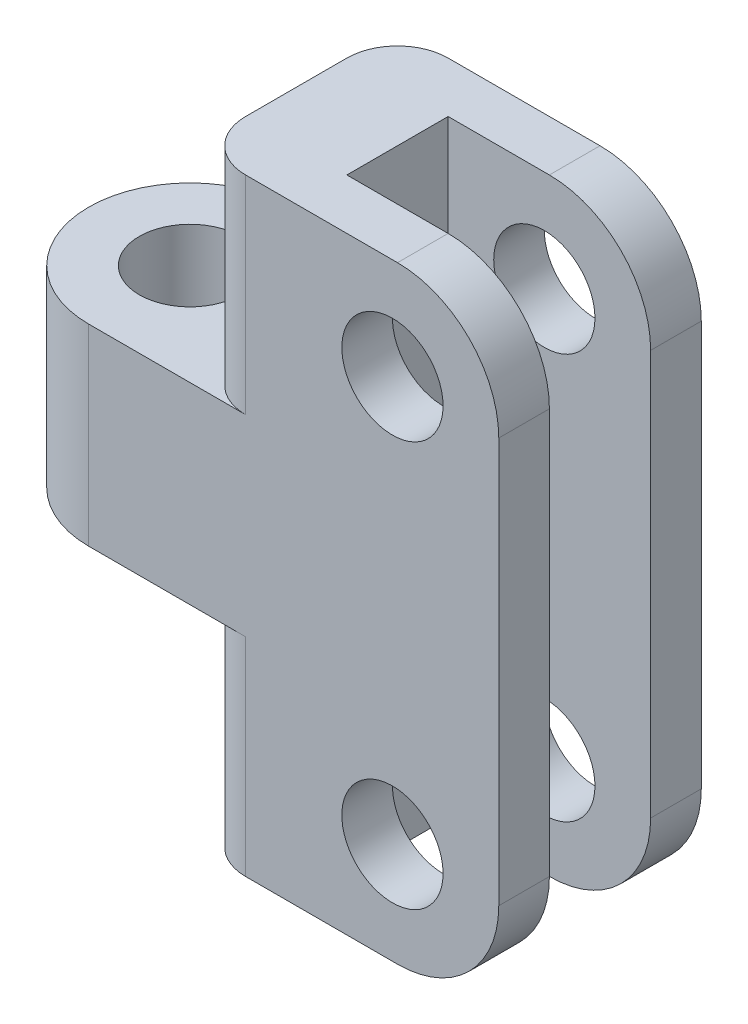
SolidWorks part; units mm, degrees
note: '?' marks a value the reader was unsure of. The reader was unsure of these and kept them because the rebuilt part matched: shared geometry of "Sketch1<3>".
material "ABS"
ref_plane "Front Plane" through (0, 0, 0) normal (0, 0, 1) x (1, 0, 0)
ref_plane "Top Plane" through (0, 0, 0) normal (0, 1, 0) x (1, 0, 0)
ref_plane "Right Plane" through (0, 0, 0) normal (1, 0, 0) x (0, 0, -1)
ref_axis "X" through (-88.99, 0, 0) along (1, 0, 0)?
ref_axis "Y" through (0, 55, 0) along (0, -1, 0)?
ref_axis "Z" through (0, 0, -88.99) along (0, 0, 1)?
sketch "Sketch1" plane through (0, 0, 0) normal (0, 1, 0) x (1, 0, 0)
  line L0 (0, 10) -> (40.5, 10)
  line L2 (40.5, -10) -> (0, -10)
  line L3 (40.5, -10) -> (40.5, -5)
  line L4 (10.5, 10) -> (10.5, -10)
  line L5 (40.5, -5) -> (20.5, -5)
  line L6 (20.5, -5) -> (20.5, 5)
  line L7 (20.5, 5) -> (40.5, 5)
  line L8 (40.5, 5) -> (40.5, 10)
  line L9 (0, 0) -> (20.5, 0) construction
  line L10 (10, 10) -> (10, -10) construction
  circle A0 centre (0, 0) radius 5
  arc A1 (0, 10) -> (0, -10) centre (0, 0) ccw
  arc A3 (0, 10) -> (0, -10) centre (0, 0) cw construction
  dimension "D1" = 10
  dimension "D2" = 5
  dimension "D3" = 10
  dimension "D4" = 30
  dimension "D5" = 10
  dimension "D6" = 0.5
extrude "Boss-Extrude1" add sketch "Sketch1" along normal mid plane 19
extrude "Boss-Extrude2" add sketch "Sketch1<3>" along normal mid plane 60
sketch "Sketch1<3>" plane through (0, 0, 0) normal (0, 1, 0) x (1, 0, 0) same geometry as "Sketch1"
sketch "Sketch2" plane through (0, 0, 10) normal (0, 0, 1) x (1, 0, 0)
  line L0 (0, 0) -> (30, 0) construction
  line L1 (0, 9.5) -> (0, -9.5) construction
  line L2 (30, 0) -> (30, 20) construction
  line L3 (30, 0) -> (30, -20) construction
  circle A0 centre (30, 20) radius 5
  circle A1 centre (30, -20) radius 5
  dimension "D1" = 10
  dimension "D2" = 20
  dimension "D3" = 30
extrude "Cut-Extrude1" cut sketch "Sketch2" against normal through all
fillet "Fillet1" radius 10 4 edges at (40.5, -30, -7.5) (40.5, -30, 7.5) (40.5, 30, -7.5) (40.5, 30, 7.5)
fillet "Fillet2" radius 5 4 edges at (10.5, -19.75, -10) (10.5, -19.75, 10) (10.5, 19.75, -10) (10.5, 19.75, 10)
